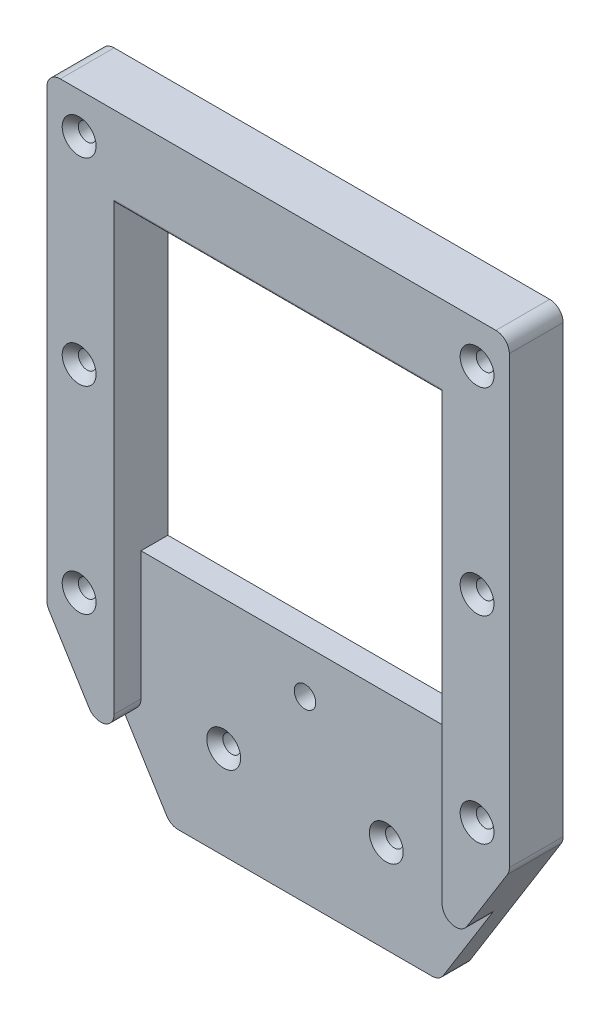
SolidWorks part; units mm, degrees
ref_plane "Front" through (0, 0, 0) normal (0, 0, 1) x (1, 0, 0)
ref_plane "Top" through (0, 0, 0) normal (0, 1, 0) x (1, 0, 0)
ref_plane "Right" through (0, 0, 0) normal (1, 0, 0) x (0, 0, -1)
sketch "Sketch1" plane through (0, 0, 0) normal (0, 0, 1) x (1, 0, 0)
  line L0 (-64.1816, 136.6499) -> (-64.1816, -35.3501)
  line L1 (-64.1816, 136.6499) -> (107.8184, 136.6499)
  line L2 (21.8184, -10.3501) -> (21.8184, -173.6926) construction
  line L4 (107.8184, 136.6499) -> (107.8184, -35.3501)
  line L5 (-39.1816, 111.6499) -> (82.8184, 111.6499)
  line L6 (-64.1816, -35.3501) -> (-28.1802, -93.2631)
  line L7 (-39.1816, -10.3501) -> (82.8184, -10.3501)
  line L8 (82.8184, 111.6499) -> (82.8184, -10.3501)
  line L9 (71.817, -93.2631) -> (107.8184, -35.3501)
  line L10 (-39.1816, 111.6499) -> (-39.1816, -10.3501)
  line L11 (-39.1816, 136.6499) -> (107.8184, 136.6499) construction
  line L12 (-39.1816, -35.3501) -> (107.8184, -35.3501) construction
  line L13 (-64.1816, -60.3501) -> (132.8184, -60.3501) construction
  line L14 (-64.1816, 161.6499) -> (-64.1816, -60.3501) construction
  line L15 (-39.1816, 136.6499) -> (-39.1816, -35.3501) construction
  line L16 (-64.1816, 161.6499) -> (132.8184, 161.6499) construction
  line L17 (132.8184, 161.6499) -> (132.8184, -60.3501) construction
  line L18 (-28.1802, -93.2631) -> (71.817, -93.2631)
  dimension "D1" = 122
  dimension "D2" = 25
  dimension "D3" = 25
  dimension "D5" = 122
  dimension "D7" = 90
  dimension "D6" = 25
extrude "Boss-Extrude1" add sketch "Sketch1" along normal blind 10
sketch "Sketch2" plane through (0, 0, 10) normal (0, 0, 1) x (1, 0, 0)
  line L1 (-64.1816, 136.6499) -> (107.8184, 136.6499)
  line L2 (-64.1816, 136.6499) -> (-64.1816, -35.3501)
  line L3 (-39.1816, 106.6499) -> (82.8184, 106.6499)
  line L5 (82.8184, 111.6499) -> (-39.1816, 111.6499) construction
  line L6 (-64.1816, -35.3501) -> (-28.1802, -93.2631) construction
  line L7 (21.8184, 136.6499) -> (21.8184, 38.8975) construction
  line L8 (82.8184, -75.5659) -> (107.8184, -35.3501)
  line L9 (82.8184, 106.6499) -> (82.8184, -75.5659)
  line L10 (-39.1816, 106.6499) -> (-39.1816, -75.5659)
  line L11 (-39.1816, -75.5659) -> (-64.1816, -35.3501)
  line L12 (107.8184, 136.6499) -> (107.8184, -35.3501)
  dimension "D1" = 5
extrude "Boss-Extrude2" add sketch "Sketch2" along normal blind 10
fillet "Fillet1" radius 1 2 edges at (21.8184, 106.6499, 20)
fillet "Fillet2" radius 5 8 edges at (-28.1802, -93.2631, 5) (-64.1816, -35.3501, 10) (71.817, -93.2631, 5) (107.8184, -35.3501, 10) (107.8184, 136.6499, 10) (-64.1816, 136.6499, 10)
sketch "Sketch4" plane through (0, 0, 20) normal (0, 0, 1) x (1, 0, 0)
  line L0 (21.8184, 165.4636) -> (21.8184, -110.4137) construction
  line L4 (-19.9436, 136.6499) -> (-107.1675, 136.6499) construction
  line L5 (102.8184, 136.6499) -> (-59.1816, 136.6499) construction
  line L6 (-8.4162, 107.6499) -> (-107.1675, 107.6499) construction
  line L7 (-39.1816, 107.6499) -> (82.8184, 107.6499) construction
  line L8 (-64.1816, 131.6499) -> (-64.1816, -33.9226) construction
  line L9 (-64.1816, 97.6848) -> (-64.1816, 160.143) construction
  line L10 (-39.1816, 85.5146) -> (-39.1816, 160.3726) construction
  line L11 (-39.1816, -58.0521) -> (-39.1816, 107.6499) construction
  line L12 (-29.1484, -10.3501) -> (-115.8777, -10.3501) construction
  line L13 (-39.1816, -10.3501) -> (82.8184, -10.3501) construction
  line L14 (-52.1816, 121.6499) -> (-52.1816, -42.347) construction
  line L15 (-115.8777, -25.3501) -> (-29.1484, -25.3501) construction
  line L16 (159.5145, -25.3501) -> (72.7852, -25.3501) construction
  line L17 (95.8184, 121.6499) -> (95.8184, -42.347) construction
  line L18 (72.7852, -10.3501) -> (159.5145, -10.3501) construction
  line L19 (82.8184, 85.5146) -> (82.8184, 160.3726) construction
  line L20 (107.8184, 97.6848) -> (107.8184, 160.143) construction
  line L21 (52.053, 107.6499) -> (150.8043, 107.6499) construction
  line L22 (63.5804, 136.6499) -> (150.8043, 136.6499) construction
  circle A0 centre (-52.1816, 121.6499) radius 3
  circle A1 centre (-52.1816, -25.3501) radius 3
  circle A2 centre (-52.1816, 48.1499) radius 3
  circle A3 centre (-8.4162, -58.6737) radius 3
  circle A4 centre (52.053, -58.6737) radius 3
  circle A5 centre (95.8184, 48.1499) radius 3
  circle A6 centre (95.8184, -25.3501) radius 3
  circle A7 centre (95.8184, 121.6499) radius 3
  circle A8 centre (21.8184, -26.8501) radius 4
  dimension "D3" = 6
  dimension "D7" = 6
  dimension "D9" = 6
  dimension "D12" = 6
  dimension "D13" = 8
  dimension "D1" = 29
  dimension "D2" = 25
  dimension "D4" = 12
  dimension "D5" = 15
  dimension "D6" = 15
  dimension "D8" = 147
  dimension "D10" = 73.5
  dimension "D11" = 74
  dimension "D14" = 16.5
other "AlignGroup1"
extrude "Cut-Extrude1" cut sketch "Sketch4" against normal up to surface (20 mm away) up to face at (21.8184, 2.3469, 0)
hole_wizard "CSK for M6 Countersunk Flat Head Screw1" positions "3DSketch2" profile "Sketch5" countersink size "M6" standard "ISO" end condition through all
sketch3d "3DSketch2"
  line L0 (-52.1816, 121.6499, 0) -> (-52.1816, 121.6499, 20) construction
  line L1 (-52.1816, 48.1499, 0) -> (-52.1816, 48.1499, 20) construction
  line L2 (-52.1816, -25.3501, 0) -> (-52.1816, -25.3501, 20) construction
  line L3 (-8.4162, -58.6737, 0) -> (-8.4162, -58.6737, 10) construction
  line L4 (52.053, -58.6737, 0) -> (52.053, -58.6737, 10) construction
  line L5 (95.8184, -25.3501, 0) -> (95.8184, -25.3501, 20) construction
  line L6 (95.8184, 48.1499, 0) -> (95.8184, 48.1499, 20) construction
  line L7 (95.8184, 121.6499, 0) -> (95.8184, 121.6499, 20) construction
  point P0 (-52.1816, 121.6499, 20)
  point P4 (-52.1816, 48.1499, 20)
  point P8 (-52.1816, -25.3501, 20)
  point P12 (-8.4162, -58.6737, 10)
  point P16 (52.053, -58.6737, 10)
  point P20 (95.8184, -25.3501, 20)
  point P24 (95.8184, 48.1499, 20)
  point P28 (95.8184, 121.6499, 20)
sketch "Sketch5" plane through (-52.1816, 121.6499, 20) normal (1, 0, 0) x (0, -1, 0)
  line L0 (0, 0) -> (0, 20)
  line L1 (0, 20) -> (3.3, 20)
  line L2 (3.3, 20) -> (3.3, 3)
  line L3 (3.3, 3) -> (6.3, 0)
  line L5 (6.3, 0) -> (0, 0)
  line L6 (-3.3, 3) -> (-6.3, 0) construction
  line L11 (0, -6.35) -> (0, 107.95) construction
  dimension "Thru Hole Dia." = 6.6
  dimension "Thru Hole Depth" = 20
  dimension "Near C'Sink Dia." = 12.6
  dimension "Near C'Sink Angle" = 90
sketch "Sketch6" plane through (0, 0, 0) normal (0, 0, -1) x (-1, 0, 0)
  line L0 (39.1816, -10.3501) -> (-82.8184, -10.3501) construction
  line L1 (-14.8902, -26.8501) -> (-18.3543, -20.8501)
  line L2 (-18.3543, -20.8501) -> (-25.2825, -20.8501)
  line L3 (-25.2825, -20.8501) -> (-28.7466, -26.8501)
  line L4 (-28.7466, -26.8501) -> (-25.2825, -32.8501)
  line L5 (-25.2825, -32.8501) -> (-18.3543, -32.8501)
  line L6 (-18.3543, -32.8501) -> (-14.8902, -26.8501)
  circle A0 centre (-21.8184, -26.8501) radius 6 construction
  dimension "D1" = 12
extrude "Cut-Extrude2" cut sketch "Sketch6" against normal blind 4
